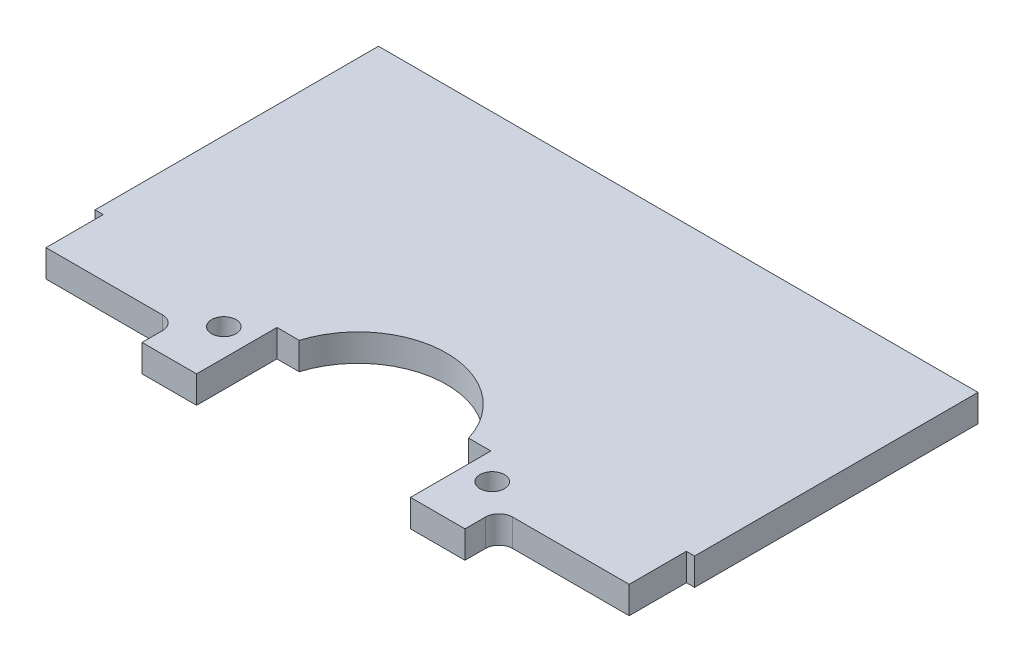
SolidWorks part; units mm, degrees
ref_plane "Front Plane" through (0, 0, 0) normal (0, 0, 1) x (1, 0, 0)
ref_plane "Top Plane" through (0, 0, 0) normal (0, 1, 0) x (1, 0, 0)
ref_plane "Right Plane" through (0, 0, 0) normal (1, 0, 0) x (0, 0, -1)
sketch "Sketch1" plane through (0, 0, 0) normal (0, 1, 0) x (1, 0, 0)
  line L0 (0, 0) -> (0, -20.1295) construction
  line L1 (-27.94, -13.208) -> (27.94, -13.208)
  line L2 (-27.94, -13.208) -> (-27.94, 13.208)
  line L3 (-27.94, 13.208) -> (27.94, 13.208)
  line L4 (27.94, -13.208) -> (27.94, 13.208)
  line L5 (-27.94, -13.208) -> (27.94, 13.208) construction
  line L6 (-27.94, 13.208) -> (27.94, -13.208) construction
  line L7 (-9.9695, -21.717) -> (-9.9695, -14.224)
  line L8 (-27.178, -18.542) -> (27.178, -18.542)
  line L9 (-27.178, -18.542) -> (-27.178, -13.208)
  line L10 (-27.178, -13.208) -> (27.178, -13.208)
  line L11 (27.178, -18.542) -> (27.178, -13.208)
  line L12 (-27.178, -18.542) -> (27.178, -13.208) construction
  line L13 (-27.178, -13.208) -> (27.178, -18.542) construction
  line L14 (-15.0495, -21.717) -> (15.0495, -21.717)
  line L15 (-15.0495, -21.717) -> (-15.0495, -18.542)
  line L16 (-15.0495, -18.542) -> (15.0495, -18.542)
  line L17 (15.0495, -21.717) -> (15.0495, -18.542)
  line L18 (-15.0495, -21.717) -> (15.0495, -18.542) construction
  line L19 (-15.0495, -18.542) -> (15.0495, -21.717) construction
  line L20 (-9.9695, -14.224) -> (9.9695, -14.224)
  line L21 (9.9695, -14.224) -> (9.9695, -21.717)
  line L22 (-12.5095, -21.717) -> (-12.5095, -16.637) construction
  line L23 (12.5095, -21.717) -> (12.5095, -16.637) construction
  line L24 (-12.5095, -16.637) -> (12.5095, -16.637) construction
  circle A0 centre (-12.5095, -16.637) radius 1.143
  circle A1 centre (12.5095, -16.637) radius 1.143
  arc A2 (-7.8945, -14.224) -> (7.8945, -14.224) centre (0, -16.637) cw
  point P0 (0, 0)
  point P8 (0, -15.875)
  dimension "D11" = 2.286
  dimension "D12" = 8.255
  dimension "D1" = 55.88
  dimension "D2" = 26.416
  dimension "D3" = 31.75
  dimension "D4" = 0.762
  dimension "D5" = 34.925
  dimension "D6" = 27.432
  dimension "D7" = 19.939
  dimension "D8" = 5.08
  dimension "D9" = 2.54
  dimension "D10" = 5.08
extrude "Boss-Extrude1" add sketch "Sketch1" along normal blind 2.54 contours L1 A2 L4 L3 L2 | L20 A2 L1 L9 L8 L7 A0 | L1 A2 L20 L21 L16 L8 L11 A1 | L15 L14 L7 L8 | L16 L21 L14 L17 region at (0, 0, -0.4105) region at (-18.6025, 0, 15.7849) region at (18.6025, 0, 15.7849) region at (-12.5095, 0, 20.1295) region at (12.5095, 0, 20.1295)
fillet "Fillet1" radius 1.27 2 edges at (-15.0495, 1.27, 18.542) (15.0495, 1.27, 18.542)
sketch "hours" plane through (0, 2.54, 0) normal (0, 1, 0) x (1, 0, 0)
  line L0 (0, 0) -> (0, -16.1969) construction
  line L1 (-17.3899, 1.193) -> (-15.3064, -0.8905)
  line L2 (15.3064, -0.8905) -> (17.3899, 1.193)
  line L3 (-7.4579, 1.808) -> (-8.5432, 4.4283)
  line L4 (7.4579, 1.808) -> (8.5432, 4.4283)
  line L5 (0, 2.6059) -> (0, 5.3999)
  line L6 (-13.7582, 1.7332) -> (-12.6317, 0.2651)
  line L7 (-10.9298, 2.7341) -> (-10.0169, 1.1528)
  line L8 (-5.4082, 3.9869) -> (-4.9448, 2.2574)
  line L9 (-2.6966, 4.2856) -> (-2.4641, 2.5197)
  line L10 (2.6966, 4.2856) -> (2.4641, 2.5197)
  line L11 (5.4082, 3.9869) -> (4.9448, 2.2574)
  line L12 (10.9298, 2.7341) -> (10.0169, 1.1528)
  line L13 (13.7582, 1.7332) -> (12.6317, 0.2651)
  line L31 (-27.94, -13.208) -> (-27.178, -13.208)
  line L32 (-27.178, -13.208) -> (-27.178, -18.542)
  line L33 (-27.178, -18.542) -> (-16.3195, -18.542)
  line L34 (-15.0495, -19.812) -> (-15.0495, -21.717)
  line L35 (-15.0495, -21.717) -> (-9.9695, -21.717)
  line L36 (-9.9695, -21.717) -> (-9.9695, -14.224)
  line L37 (-9.9695, -14.224) -> (-7.8945, -14.224)
  line L38 (7.8945, -14.224) -> (9.9695, -14.224)
  line L39 (9.9695, -14.224) -> (9.9695, -21.717)
  line L40 (9.9695, -21.717) -> (15.0495, -21.717)
  line L41 (15.0495, -21.717) -> (15.0495, -19.812)
  line L42 (16.3195, -18.542) -> (27.178, -18.542)
  line L43 (27.178, -18.542) -> (27.178, -13.208)
  line L44 (27.178, -13.208) -> (27.94, -13.208)
  line L45 (27.94, -13.208) -> (27.94, 13.208)
  line L46 (27.94, 13.208) -> (-27.94, 13.208)
  line L47 (-27.94, 13.208) -> (-27.94, -13.208)
  line L48 (-27.94, -13.208) -> (-27.178, -13.208)
  line L49 (-27.178, -13.208) -> (-27.178, -18.542)
  line L50 (-27.178, -18.542) -> (-16.3195, -18.542)
  line L51 (-15.0495, -19.812) -> (-15.0495, -21.717)
  line L52 (-15.0495, -21.717) -> (-9.9695, -21.717)
  line L53 (-9.9695, -21.717) -> (-9.9695, -14.224)
  line L54 (-9.9695, -14.224) -> (-7.8945, -14.224)
  line L55 (7.8945, -14.224) -> (9.9695, -14.224)
  line L56 (9.9695, -14.224) -> (9.9695, -21.717)
  line L57 (9.9695, -21.717) -> (15.0495, -21.717)
  line L58 (15.0495, -21.717) -> (15.0495, -19.812)
  line L59 (16.3195, -18.542) -> (27.178, -18.542)
  line L60 (27.178, -18.542) -> (27.178, -13.208)
  line L61 (27.178, -13.208) -> (27.94, -13.208)
  line L62 (27.94, -13.208) -> (27.94, 13.208)
  line L63 (27.94, 13.208) -> (-27.94, 13.208)
  line L64 (-27.94, 13.208) -> (-27.94, -13.208)
  arc A0 (-14.7549, -2.0345) -> (14.7549, -2.0345) centre (0, -32.6457) cw
  arc A1 (-15.3064, -0.8905) -> (15.3064, -0.8905) centre (0, -32.6457) cw
  arc A2 (-17.3899, 1.193) -> (17.3899, 1.193) centre (0, -32.6457) cw
  arc A3 (-16.5195, 1.6264) -> (16.5195, 1.6264) centre (0, -32.6457) cw construction
  arc A4 (-16.0784, 0.7111) -> (16.0784, 0.7111) centre (0, -32.6457) cw
  circle A5 centre (-12.5095, -16.637) radius 1.143 construction
  circle A6 centre (12.5095, -16.637) radius 1.143 construction
  circle A7 centre (-12.5095, -16.637) radius 1.143
  arc A8 (-15.0495, -19.812) -> (-16.3195, -18.542) centre (-16.3195, -19.812) ccw
  arc A9 (7.8945, -14.224) -> (-7.8945, -14.224) centre (0, -16.637) ccw
  arc A10 (16.3195, -18.542) -> (15.0495, -19.812) centre (16.3195, -19.812) ccw
  arc A11 (-15.0495, -19.812) -> (-16.3195, -18.542) centre (-16.3195, -19.812) ccw
  arc A12 (7.8945, -14.224) -> (-7.8945, -14.224) centre (0, -16.637) ccw
  arc A13 (16.3195, -18.542) -> (15.0495, -19.812) centre (16.3195, -19.812) ccw
  circle A14 centre (12.5095, -16.637) radius 1.143
  dimension "D1" = 33.9816
  dimension "D3" = 16.4488
  dimension "D5" = 22.5
  dimension "D6" = 22.5
  dimension "D7" = 22.5
  dimension "D8" = 1.778
  dimension "D9" = 7.5
  dimension "D10" = 7.5
  dimension "D11" = 7.5
  dimension "D12" = 7.5
  dimension "D13" = 7.5
  dimension "D14" = 7.5
  dimension "D15" = 7.5
  dimension "D16" = 7.5
  dimension "D2" = 1.27
  dimension "D4" = 2.794
  dimension "D17" = 0
sketch "minutes" plane through (0, 0, 0) normal (0, 1, 0) x (1, 0, 0)
  line L0 (0, 0) -> (0, -16.1969) construction
  line L1 (-17.3899, 1.193) -> (-15.3064, -0.8905)
  line L2 (15.3064, -0.8905) -> (17.3899, 1.193)
  line L3 (-4.9448, 2.2574) -> (-5.6729, 4.9746)
  line L4 (-8.1488, 3.4762) -> (-7.4579, 1.808)
  line L5 (0, 2.6059) -> (0, 5.3999)
  line L6 (-13.7582, 1.7332) -> (-12.6317, 0.2651)
  line L7 (-11.4505, 3.6359) -> (-10.0169, 1.1528)
  line L8 (2.6966, 4.2856) -> (2.4641, 2.5197)
  line L9 (-2.6966, 4.2856) -> (-2.4641, 2.5197)
  line L10 (4.9448, 2.2574) -> (5.6729, 4.9746)
  line L11 (8.1488, 3.4762) -> (7.4579, 1.808)
  line L12 (11.4505, 3.6359) -> (10.0169, 1.1528)
  line L13 (13.7582, 1.7332) -> (12.6317, 0.2651)
  line L14 (17.3899, 1.193) -> (15.3064, -0.8905)
  line L48 (-27.94, -13.208) -> (-27.178, -13.208)
  line L49 (-27.178, -13.208) -> (-27.178, -18.542)
  line L50 (-27.178, -18.542) -> (-16.3195, -18.542)
  line L51 (-15.0495, -19.812) -> (-15.0495, -21.717)
  line L52 (-15.0495, -21.717) -> (-9.9695, -21.717)
  line L53 (-9.9695, -21.717) -> (-9.9695, -14.224)
  line L54 (-9.9695, -14.224) -> (-7.8945, -14.224)
  line L55 (7.8945, -14.224) -> (9.9695, -14.224)
  line L56 (9.9695, -14.224) -> (9.9695, -21.717)
  line L57 (9.9695, -21.717) -> (15.0495, -21.717)
  line L58 (15.0495, -21.717) -> (15.0495, -19.812)
  line L59 (16.3195, -18.542) -> (27.178, -18.542)
  line L60 (27.178, -18.542) -> (27.178, -13.208)
  line L61 (27.178, -13.208) -> (27.94, -13.208)
  line L62 (27.94, -13.208) -> (27.94, 13.208)
  line L63 (27.94, 13.208) -> (-27.94, 13.208)
  line L64 (-27.94, 13.208) -> (-27.94, -13.208)
  arc A0 (-14.7549, -2.0345) -> (14.7549, -2.0345) centre (0, -32.6457) cw
  arc A1 (-15.3064, -0.8905) -> (15.3064, -0.8905) centre (0, -32.6457) cw
  arc A2 (-17.3899, 1.193) -> (17.3899, 1.193) centre (0, -32.6457) cw
  arc A3 (-16.5195, 1.6264) -> (16.5195, 1.6264) centre (0, -32.6457) cw construction
  arc A4 (-16.6343, 0.4374) -> (16.6343, 0.4374) centre (0, -32.6457) cw
  arc A5 (-16.0784, 0.7111) -> (16.0784, 0.7111) centre (0, -32.6457) cw construction
  circle A6 centre (-12.5095, -16.637) radius 1.143 construction
  circle A7 centre (-12.5095, -16.637) radius 1.143
  circle A8 centre (12.5095, -16.637) radius 1.143 construction
  arc A11 (-15.0495, -19.812) -> (-16.3195, -18.542) centre (-16.3195, -19.812) ccw
  arc A12 (7.8945, -14.224) -> (-7.8945, -14.224) centre (0, -16.637) ccw
  arc A13 (16.3195, -18.542) -> (15.0495, -19.812) centre (16.3195, -19.812) ccw
  circle A14 centre (12.5095, -16.637) radius 1.143
  dimension "D1" = 33.9816
  dimension "D3" = 16.4488
  dimension "D5" = 15
  dimension "D6" = 15
  dimension "D7" = 15
  dimension "D8" = 1.778
  dimension "D9" = 7.5
  dimension "D10" = 7.5
  dimension "D11" = 7.5
  dimension "D2" = 1.27
  dimension "D4" = 2.794
